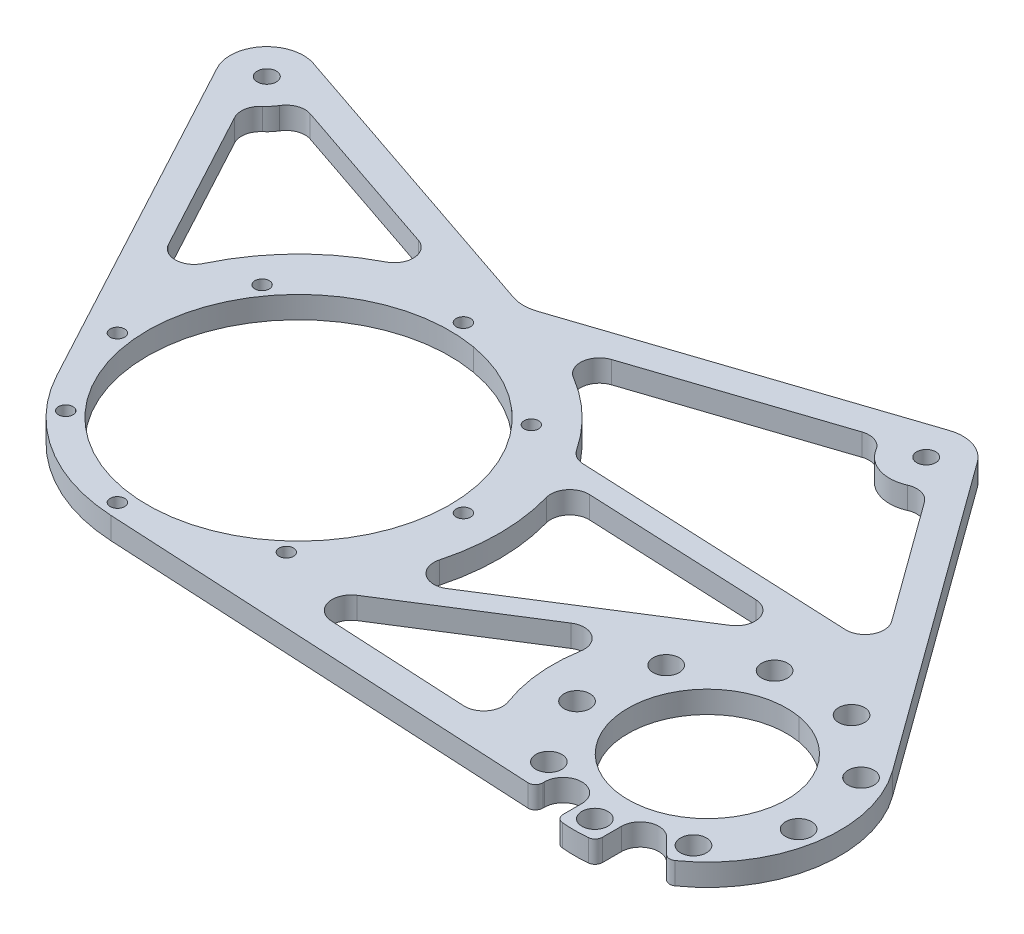
SolidWorks part; units mm, degrees
material "6061-T6 (SS)"
ref_plane "X-Y Datum" through (0, 0, 0) normal (0, 0, 1) x (1, 0, 0)
ref_plane "X-Z Datum" through (0, 0, 0) normal (0, 1, 0) x (1, 0, 0)
ref_plane "Y-Z Datum" through (0, 0, 0) normal (1, 0, 0) x (0, 0, -1)
sketch "Sketch2" plane through (0, -92.4008, 0) normal (0, 1, 0) x (1, 0, 0)
  line L0 (-504.3573, -163.648) -> (-504.3573, -170.2207) construction
  line L1 (-490.6797, -170.2207) -> (-490.6797, -163.648) construction
  line L2 (-479.5835, -159.0518) -> (-474.3186, -164.3167) construction
  line L3 (-504.3573, -163.648) -> (-504.3573, -170.2207)
  line L4 (-490.6797, -170.2207) -> (-490.6797, -163.648)
  line L5 (-479.5835, -159.0518) -> (-474.3186, -164.3167)
  line L6 (-777.24, 12.7) -> (-548.64, 12.7)
  line L7 (-538.3646, 7.4636) -> (-460.3214, -99.9818)
  line L9 (-788.4277, -6.0104) -> (-723.8302, -126.2521)
  line L10 (-517.3573, -164.225) -> (-517.3573, -163.648) construction
  line L11 (-517.3573, -164.225) -> (-517.3573, -163.648)
  line L12 (-672.5249, -158.7794) -> (-519.8973, -166.765)
  line L13 (-669.29, -96.9515) -> (-497.5185, -127) construction
  arc A0 (-521.206, -166.4019) -> (-517.3573, -164.225) centre (-519.8973, -164.225) ccw construction
  arc A1 (-504.3573, -163.648) -> (-517.3573, -163.648) centre (-510.8573, -163.648) ccw construction
  arc A2 (-504.3573, -170.2207) -> (-502.0687, -172.7483) centre (-501.8173, -170.2207) ccw construction
  arc A3 (-502.0687, -172.7483) -> (-492.9683, -172.7483) centre (-497.5185, -127) ccw construction
  arc A4 (-492.9683, -172.7483) -> (-490.6797, -170.2207) centre (-493.2197, -170.2207) ccw construction
  arc A5 (-479.5835, -159.0518) -> (-490.6797, -163.648) centre (-484.1797, -163.648) ccw construction
  arc A6 (-474.3186, -164.3167) -> (-471.0608, -164.5979) centre (-472.5226, -162.5207) ccw construction
  arc A7 (-471.0608, -164.5979) -> (-521.206, -166.4019) centre (-497.5185, -127) ccw construction
  circle A8 centre (-669.29, -96.9515) radius 52.3875 construction
  circle A9 centre (-669.29, -96.9515) radius 61.9125 construction
  circle A10 centre (-548.64, 0) radius 12.7 construction
  circle A11 centre (-777.24, 0) radius 12.7 construction
  arc A12 (-521.206, -166.4019) -> (-517.3573, -164.225) centre (-519.8973, -164.225) ccw
  arc A13 (-504.3573, -163.648) -> (-517.3573, -163.648) centre (-510.8573, -163.648) ccw
  arc A14 (-504.3573, -170.2207) -> (-502.0687, -172.7483) centre (-501.8173, -170.2207) ccw
  arc A15 (-502.0687, -172.7483) -> (-492.9683, -172.7483) centre (-497.5185, -127) ccw
  arc A16 (-492.9683, -172.7483) -> (-490.6797, -170.2207) centre (-493.2197, -170.2207) ccw
  arc A17 (-479.5835, -159.0518) -> (-490.6797, -163.648) centre (-484.1797, -163.648) ccw
  arc A18 (-474.3186, -164.3167) -> (-471.0608, -164.5979) centre (-472.5226, -162.5207) ccw
  arc A19 (-471.0608, -164.5979) -> (-521.206, -166.4019) centre (-497.5185, -127) ccw
  circle A20 centre (-669.29, -96.9515) radius 52.3875
  circle A21 centre (-669.29, -96.9515) radius 61.9125
  circle A22 centre (-548.64, 0) radius 12.7
  circle A23 centre (-777.24, 0) radius 12.7
  circle A24 centre (-711.7607, -135.1923) radius 2.5 construction
  circle A25 centre (-726.1269, -102.9253) radius 2.5 construction
  circle A26 centre (-715.5253, -63.3596) radius 2.5 construction
  circle A27 centre (-669.29, -39.8015) radius 2.5 construction
  circle A28 centre (-626.8193, -58.7107) radius 2.5 construction
  circle A29 centre (-612.14, -96.9515) radius 2.5 construction
  circle A30 centre (-631.0492, -139.4222) radius 2.5 construction
  circle A31 centre (-675.2638, -153.7884) radius 2.5 construction
  circle A32 centre (-711.7607, -135.1923) radius 2.5
  circle A33 centre (-726.1269, -102.9253) radius 2.5
  circle A34 centre (-715.5253, -63.3596) radius 2.5
  circle A35 centre (-669.29, -39.8015) radius 2.5
  circle A36 centre (-626.8193, -58.7107) radius 2.5
  circle A37 centre (-612.14, -96.9515) radius 2.5
  circle A38 centre (-631.0492, -139.4222) radius 2.5
  circle A39 centre (-675.2638, -153.7884) radius 2.5
  circle A40 centre (-497.5185, -127) radius 27.4955 construction
  circle A41 centre (-497.5185, -127) radius 27.4955
  circle A42 centre (-522.5872, -156.8757) radius 4.5 construction
  circle A43 centre (-535.926, -133.7723) radius 4.5 construction
  circle A44 centre (-531.2935, -107.5) radius 4.5 construction
  circle A45 centre (-510.8573, -90.352) radius 4.5 construction
  circle A46 centre (-484.1797, -90.352) radius 4.5 construction
  circle A47 centre (-463.7435, -107.5) radius 4.5 construction
  circle A48 centre (-459.111, -133.7723) radius 4.5 construction
  circle A49 centre (-472.4498, -156.8757) radius 4.5 construction
  circle A50 centre (-497.5185, -166) radius 4.5 construction
  circle A51 centre (-522.5872, -156.8757) radius 4.5
  circle A52 centre (-535.926, -133.7723) radius 4.5
  circle A53 centre (-531.2935, -107.5) radius 4.5
  circle A54 centre (-510.8573, -90.352) radius 4.5
  circle A55 centre (-484.1797, -90.352) radius 4.5
  circle A56 centre (-463.7435, -107.5) radius 4.5
  circle A57 centre (-459.111, -133.7723) radius 4.5
  circle A58 centre (-472.4498, -156.8757) radius 4.5
  circle A59 centre (-497.5185, -166) radius 4.5
  circle A60 centre (-777.24, 0) radius 3.3
  circle A61 centre (-548.64, 0) radius 3.3
  dimension "D1" = 6.6
  dimension "D2" = 6.6
extrude "Boss-Extrude1" add sketch "Sketch2" along normal blind 7.62 contours A21 A39 A38 A37 A36 A35 A34 A33 A32 A20 | A23 L9 A21 A19 L7 A22 L6 | A18 A19 A12 L11 A13 L3 A14 A15 A16 L4 A17 L5 A59 A58 A57 A56 A55 A54 A53 A52 A51 A41 | A23 A60 | A22 A61 | L13 A21 L12 A12 A19 region at (-510.8573, -92.4008, 155.8477) region at (-583.65, -92.4008, 141.3142) region at (-701.5034, -92.4008, 147.7617) region at (-625.8887, -92.4008, 39.3924) region at (-787.8317, -92.4008, -6.3332) region at (-536.903, -92.4008, -3.8128)
sketch "Sketch3" plane through (0, -92.4008, 0) normal (0, -1, 0) x (1, 0, 0)
  line L5 (-672.5249, 158.7794) -> (-519.8973, 166.765) construction
  line L6 (-788.4277, 6.0104) -> (-723.8302, 126.2521) construction
  line L7 (-538.3646, -7.4636) -> (-460.3214, 99.9818) construction
  line L16 (-777.24, -12.7) -> (-548.64, -12.7) construction
  line L19 (-474.3186, 164.3167) -> (-479.5835, 159.0518)
  line L20 (-490.6797, 163.648) -> (-490.6797, 170.2207)
  line L21 (-504.3573, 170.2207) -> (-504.3573, 163.648)
  line L22 (-517.3573, 163.648) -> (-517.3573, 164.225)
  line L23 (-474.3186, 164.3167) -> (-479.5835, 159.0518)
  line L24 (-490.6797, 163.648) -> (-490.6797, 170.2207)
  line L25 (-504.3573, 170.2207) -> (-504.3573, 163.648)
  line L26 (-517.3573, 163.648) -> (-517.3573, 164.225)
  line L28 (-672.5249, 158.7794) -> (-519.8973, 166.765)
  line L29 (-788.4277, 6.0104) -> (-723.8302, 126.2521)
  line L30 (-538.3646, -7.4636) -> (-460.3214, 99.9818)
  line L31 (-777.24, -12.7) -> (-548.64, -12.7)
  line L32 (-773.1635, -12.028) -> (-664.0361, 24.9569)
  line L33 (-664.0361, 24.9569) -> (-552.6443, -12.0522)
  circle A3 centre (-777.24, 0) radius 12.7
  circle A5 centre (-777.24, 0) radius 12.7
  circle A7 centre (-548.64, 0) radius 12.7
  circle A9 centre (-548.64, 0) radius 12.7
  circle A11 centre (-669.29, 96.9515) radius 61.9125
  circle A13 centre (-669.29, 96.9515) radius 61.9125
  circle A15 centre (-669.29, 96.9515) radius 52.3875
  circle A17 centre (-669.29, 96.9515) radius 52.3875
  circle A19 centre (-497.5185, 127) radius 27.4955
  circle A21 centre (-497.5185, 127) radius 27.4955
  circle A23 centre (-675.2638, 153.7884) radius 2.5
  circle A25 centre (-675.2638, 153.7884) radius 2.5
  circle A27 centre (-631.0492, 139.4222) radius 2.5
  circle A29 centre (-631.0492, 139.4222) radius 2.5
  circle A31 centre (-612.14, 96.9515) radius 2.5
  circle A33 centre (-612.14, 96.9515) radius 2.5
  circle A35 centre (-626.8193, 58.7107) radius 2.5
  circle A37 centre (-626.8193, 58.7107) radius 2.5
  circle A39 centre (-669.29, 39.8015) radius 2.5
  circle A41 centre (-669.29, 39.8015) radius 2.5
  circle A43 centre (-715.5253, 63.3596) radius 2.5
  circle A46 centre (-715.5253, 63.3596) radius 2.5
  circle A47 centre (-726.1269, 102.9253) radius 2.5
  circle A48 centre (-726.1269, 102.9253) radius 2.5
  circle A49 centre (-711.7607, 135.1923) radius 2.5
  circle A50 centre (-711.7607, 135.1923) radius 2.5
  circle A51 centre (-531.2935, 107.5) radius 4.5
  circle A52 centre (-531.2935, 107.5) radius 4.5
  circle A68 centre (-535.926, 133.7723) radius 4.5
  circle A69 centre (-535.926, 133.7723) radius 4.5
  circle A70 centre (-522.5872, 156.8757) radius 4.5
  circle A71 centre (-522.5872, 156.8757) radius 4.5
  circle A72 centre (-548.64, 0) radius 3.3
  circle A73 centre (-548.64, 0) radius 3.3
  circle A74 centre (-777.24, 0) radius 3.3
  circle A75 centre (-777.24, 0) radius 3.3
  circle A76 centre (-497.5185, 166) radius 4.5
  circle A77 centre (-497.5185, 166) radius 4.5
  circle A78 centre (-472.4498, 156.8757) radius 4.5
  circle A79 centre (-472.4498, 156.8757) radius 4.5
  circle A80 centre (-459.111, 133.7723) radius 4.5
  circle A81 centre (-459.111, 133.7723) radius 4.5
  circle A82 centre (-463.7435, 107.5) radius 4.5
  circle A83 centre (-463.7435, 107.5) radius 4.5
  circle A84 centre (-484.1797, 90.352) radius 4.5
  circle A85 centre (-484.1797, 90.352) radius 4.5
  circle A86 centre (-510.8573, 90.352) radius 4.5
  circle A87 centre (-510.8573, 90.352) radius 4.5
  arc A95 (-521.206, 166.4019) -> (-471.0608, 164.5979) centre (-497.5185, 127) ccw
  arc A96 (-471.0608, 164.5979) -> (-474.3186, 164.3167) centre (-472.5226, 162.5207) ccw
  arc A97 (-490.6797, 163.648) -> (-479.5835, 159.0518) centre (-484.1797, 163.648) ccw
  arc A98 (-490.6797, 170.2207) -> (-492.9683, 172.7483) centre (-493.2197, 170.2207) ccw
  arc A99 (-492.9683, 172.7483) -> (-502.0687, 172.7483) centre (-497.5185, 127) ccw
  arc A100 (-502.0687, 172.7483) -> (-504.3573, 170.2207) centre (-501.8173, 170.2207) ccw
  arc A101 (-517.3573, 163.648) -> (-504.3573, 163.648) centre (-510.8573, 163.648) ccw
  arc A102 (-517.3573, 164.225) -> (-521.206, 166.4019) centre (-519.8973, 164.225) ccw
  arc A103 (-521.206, 166.4019) -> (-471.0608, 164.5979) centre (-497.5185, 127) ccw
  arc A104 (-471.0608, 164.5979) -> (-474.3186, 164.3167) centre (-472.5226, 162.5207) ccw
  arc A105 (-490.6797, 163.648) -> (-479.5835, 159.0518) centre (-484.1797, 163.648) ccw
  arc A106 (-490.6797, 170.2207) -> (-492.9683, 172.7483) centre (-493.2197, 170.2207) ccw
  arc A107 (-492.9683, 172.7483) -> (-502.0687, 172.7483) centre (-497.5185, 127) ccw
  arc A108 (-502.0687, 172.7483) -> (-504.3573, 170.2207) centre (-501.8173, 170.2207) ccw
  arc A109 (-517.3573, 163.648) -> (-504.3573, 163.648) centre (-510.8573, 163.648) ccw
  arc A110 (-517.3573, 164.225) -> (-521.206, 166.4019) centre (-519.8973, 164.225) ccw
  point P96 (-664.0361, 24.9569)
  line M47 (-777.24, -12.7) -> (-548.64, -12.7)
  dimension "D24" = 0
  dimension "D25" = 0
  dimension "D26" = 109.1275
  dimension "D27" = 36.9849
  dimension "D1" = 0
  dimension "D2" = 0
  dimension "D3" = 0
  dimension "D4" = 0
  dimension "D5" = 0
  dimension "D6" = 0
  dimension "D7" = 0
  dimension "D8" = 0
  dimension "D9" = 0
  dimension "D10" = 0
  dimension "D11" = 0
  dimension "D12" = 0
  dimension "D13" = 0
  dimension "D14" = 0
  dimension "D15" = 0
  dimension "D16" = 0
  dimension "D17" = 0
  dimension "D18" = 0
  dimension "D19" = 0
  dimension "D20" = 0
  dimension "D21" = 0
  dimension "D22" = 0
  dimension "D23" = 0
ref_point "Point1"
ref_point "Point2"
ref_plane "Plane1" through (-669.29, -92.4008, 96.9515) normal (0.985, 0, 0.1723) x (0.1723, 0, -0.985)
ref_plane "Plane2" through (-497.5185, -92.4008, 127) normal (-0.985, 0, -0.1723) x (-0.1723, 0, 0.985)
split line "Split Line1"
split line "Split Line2"
ref_axis "Axis1" through (-669.29, -84.7808, 96.9515) along (0, -1, 0)
ref_axis "Axis2" through (-497.5185, -84.7808, 127) along (0, -1, 0)
extrude "Cut-Extrude1" cut sketch "Sketch3" against normal through all contours A9 L33 L32 A5 M47 region at (-663.2926, -92.4008, -0.149)
fillet "Fillet2" radius 12.7 1 edges at (-664.0361, -88.5908, 24.9569)
sketch "Sketch4" plane through (0, -92.4008, 0) normal (0, -1, 0) x (1, 0, 0)
  line L0 (-672.5249, 158.7794) -> (-519.8973, 166.765) construction
  line L1 (-538.3646, -7.4636) -> (-460.3214, 99.9818) construction
  line L2 (-788.4277, 6.0104) -> (-723.8302, 126.2521) construction
  line L3 (-773.1635, -12.028) -> (-664.0361, 24.9569) construction
  line L4 (-517.3573, 163.648) -> (-517.3573, 164.225)
  line L5 (-474.3186, 164.3167) -> (-479.5835, 159.0518)
  line L6 (-490.6797, 163.648) -> (-490.6797, 170.2207)
  line L7 (-504.3573, 170.2207) -> (-504.3573, 163.648)
  line L8 (-517.3573, 163.648) -> (-517.3573, 164.225)
  line L9 (-474.3186, 164.3167) -> (-479.5835, 159.0518)
  line L10 (-490.6797, 163.648) -> (-490.6797, 170.2207)
  line L11 (-504.3573, 170.2207) -> (-504.3573, 163.648)
  line L12 (-664.0361, 24.9569) -> (-552.6443, -12.0522) construction
  line L13 (-777.24, -12.7) -> (-548.64, -12.7) construction
  line L14 (-672.5249, 158.7794) -> (-519.8973, 166.765)
  line L15 (-538.3646, -7.4636) -> (-460.3214, 99.9818)
  line L16 (-788.4277, 6.0104) -> (-723.8302, 126.2521)
  line L17 (-773.1635, -12.028) -> (-664.0361, 24.9569)
  line L18 (-664.0361, 24.9569) -> (-552.6443, -12.0522)
  line L19 (-777.24, -12.7) -> (-548.64, -12.7)
  line L20 (-736.857, 80.5359) -> (-782.5267, -4.4737)
  line L21 (-782.5267, -4.4737) -> (-683.866, 28.9639)
  line L22 (-542.9794, 155.3834) -> (-623.3807, 151.1768)
  line L23 (-623.3807, 151.1768) -> (-544.5668, 101.3333)
  line L24 (-610.432, 133.9718) -> (-514.4002, 73.2395)
  line L25 (-514.4002, 73.2395) -> (-605.5685, 69.1245)
  line L26 (-648.653, 30.5521) -> (-561.2496, 1.5129)
  line L27 (-609.5837, 61.3155) -> (-497.2823, 66.3843)
  line L28 (-497.2823, 66.3843) -> (-539.2721, 8.5751)
  circle A1 centre (-669.29, 96.9515) radius 52.3875
  circle A2 centre (-669.29, 96.9515) radius 52.3875
  circle A3 centre (-669.29, 96.9515) radius 61.9125
  circle A4 centre (-669.29, 96.9515) radius 61.9125
  circle A5 centre (-548.64, 0) radius 12.7
  circle A6 centre (-548.64, 0) radius 12.7
  circle A7 centre (-777.24, 0) radius 12.7
  circle A8 centre (-777.24, 0) radius 12.7
  circle A9 centre (-669.29, 39.8015) radius 2.5
  circle A10 centre (-669.29, 39.8015) radius 2.5
  circle A11 centre (-626.8193, 58.7107) radius 2.5
  circle A12 centre (-626.8193, 58.7107) radius 2.5
  circle A13 centre (-612.14, 96.9515) radius 2.5
  circle A14 centre (-612.14, 96.9515) radius 2.5
  circle A15 centre (-631.0492, 139.4222) radius 2.5
  circle A16 centre (-631.0492, 139.4222) radius 2.5
  circle A17 centre (-675.2638, 153.7884) radius 2.5
  circle A18 centre (-675.2638, 153.7884) radius 2.5
  circle A19 centre (-497.5185, 127) radius 27.4955
  circle A20 centre (-497.5185, 127) radius 27.4955
  circle A21 centre (-535.926, 133.7723) radius 4.5
  circle A22 centre (-535.926, 133.7723) radius 4.5
  circle A23 centre (-531.2935, 107.5) radius 4.5
  circle A24 centre (-531.2935, 107.5) radius 4.5
  circle A25 centre (-711.7607, 135.1923) radius 2.5
  circle A26 centre (-711.7607, 135.1923) radius 2.5
  circle A27 centre (-726.1269, 102.9253) radius 2.5
  circle A28 centre (-726.1269, 102.9253) radius 2.5
  circle A29 centre (-715.5253, 63.3596) radius 2.5
  circle A30 centre (-715.5253, 63.3596) radius 2.5
  circle A31 centre (-472.4498, 156.8757) radius 4.5
  circle A32 centre (-472.4498, 156.8757) radius 4.5
  circle A33 centre (-497.5185, 166) radius 4.5
  circle A34 centre (-497.5185, 166) radius 4.5
  circle A35 centre (-777.24, 0) radius 3.3
  circle A36 centre (-777.24, 0) radius 3.3
  circle A37 centre (-548.64, 0) radius 3.3
  circle A38 centre (-548.64, 0) radius 3.3
  circle A39 centre (-522.5872, 156.8757) radius 4.5
  circle A40 centre (-522.5872, 156.8757) radius 4.5
  circle A41 centre (-510.8573, 90.352) radius 4.5
  circle A42 centre (-510.8573, 90.352) radius 4.5
  circle A43 centre (-484.1797, 90.352) radius 4.5
  circle A44 centre (-484.1797, 90.352) radius 4.5
  circle A45 centre (-463.7435, 107.5) radius 4.5
  circle A46 centre (-463.7435, 107.5) radius 4.5
  circle A47 centre (-459.111, 133.7723) radius 4.5
  circle A48 centre (-459.111, 133.7723) radius 4.5
  arc A49 (-683.866, 28.9639) -> (-736.857, 80.5359) centre (-669.29, 96.9515) cw
  arc A50 (-542.9794, 155.3834) -> (-544.5668, 101.3333) centre (-497.5185, 127) ccw
  arc A51 (-610.432, 133.9718) -> (-605.5685, 69.1245) centre (-669.29, 96.9515) cw
  arc A52 (-648.653, 30.5521) -> (-609.5837, 61.3155) centre (-669.29, 96.9515) ccw
  arc A56 (-517.3573, 164.225) -> (-521.206, 166.4019) centre (-519.8973, 164.225) ccw
  arc A57 (-521.206, 166.4019) -> (-471.0608, 164.5979) centre (-497.5185, 127) ccw
  arc A58 (-471.0608, 164.5979) -> (-474.3186, 164.3167) centre (-472.5226, 162.5207) ccw
  arc A59 (-490.6797, 163.648) -> (-479.5835, 159.0518) centre (-484.1797, 163.648) ccw
  arc A60 (-490.6797, 170.2207) -> (-492.9683, 172.7483) centre (-493.2197, 170.2207) ccw
  arc A61 (-492.9683, 172.7483) -> (-502.0687, 172.7483) centre (-497.5185, 127) ccw
  arc A62 (-502.0687, 172.7483) -> (-504.3573, 170.2207) centre (-501.8173, 170.2207) ccw
  arc A63 (-517.3573, 163.648) -> (-504.3573, 163.648) centre (-510.8573, 163.648) ccw
  arc A64 (-517.3573, 164.225) -> (-521.206, 166.4019) centre (-519.8973, 164.225) ccw
  arc A65 (-521.206, 166.4019) -> (-471.0608, 164.5979) centre (-497.5185, 127) ccw
  arc A66 (-471.0608, 164.5979) -> (-474.3186, 164.3167) centre (-472.5226, 162.5207) ccw
  arc A67 (-490.6797, 163.648) -> (-479.5835, 159.0518) centre (-484.1797, 163.648) ccw
  arc A68 (-490.6797, 170.2207) -> (-492.9683, 172.7483) centre (-493.2197, 170.2207) ccw
  arc A69 (-492.9683, 172.7483) -> (-502.0687, 172.7483) centre (-497.5185, 127) ccw
  arc A70 (-502.0687, 172.7483) -> (-504.3573, 170.2207) centre (-501.8173, 170.2207) ccw
  arc A71 (-517.3573, 163.648) -> (-504.3573, 163.648) centre (-510.8573, 163.648) ccw
  point P115 (-561.2494, 1.5144)
  point P117 (-647.1131, 28.9639)
  point P118 (-645.4628, 29.9334)
  dimension "D26" = 7.62
  dimension "D29" = 7.62
  dimension "D30" = 7.62
  dimension "D35" = 10.16
  dimension "D39" = 7.62
  dimension "D27" = 10.16
  dimension "D28" = 10.16
  dimension "D31" = 10.16
  dimension "D32" = 7.62
  dimension "D33" = 93.2524
  dimension "D34" = 49.8435
  dimension "D36" = 91.1683
  dimension "D37" = 4.1149
  dimension "D38" = 10.16
  dimension "D40" = 7.62
  dimension "D1" = 0
  dimension "D2" = 0
  dimension "D3" = 0
  dimension "D4" = 0
  dimension "D5" = 0
  dimension "D6" = 0
  dimension "D7" = 0
  dimension "D8" = 0
  dimension "D9" = 0
  dimension "D10" = 0
  dimension "D11" = 0
  dimension "D12" = 0
  dimension "D13" = 0
  dimension "D14" = 0
  dimension "D15" = 0
  dimension "D16" = 0
  dimension "D17" = 0
  dimension "D18" = 0
  dimension "D19" = 0
  dimension "D20" = 0
  dimension "D21" = 0
  dimension "D22" = 0
  dimension "D23" = 0
  dimension "D24" = 0
  dimension "D25" = 0
extrude "Cut-Extrude2" cut sketch "Sketch4" against normal through all contours L21 A49 L20 A8 | A52 L26 A6 L28 L27 | L24 A51 L25 | A50 L22 L23 region at (-736.5247, -92.4008, 33.3857) region at (-569.3531, -92.4008, 38.1987) region at (-573.6295, -92.4008, 137.0229) region at (-573.0084, -92.4008, 90.7995)
fillet "Fillet3" radius 6.604 15 edges at (-544.5668, -88.5908, 101.3333) (-542.9794, -88.5908, 155.3834) (-623.3807, -88.5908, 151.1768) (-514.4002, -88.5908, 73.2395) (-605.5685, -88.5908, 69.1245) (-610.432, -88.5908, 133.9718) (-497.2823, -88.5908, 66.3843) (-609.5837, -88.5908, 61.3155) (-648.653, -88.5908, 30.5521) (-561.2496, -88.5908, 1.5129) (-539.2721, -88.5908, 8.5751) (-764.6397, -88.5908, 1.5885) (-773.5886, -88.5908, 12.1638) (-683.866, -88.5908, 28.9639) (-736.857, -88.5908, 80.5359)
split line "Split Line3"
sketch "Sketch2<4>" plane through (0, -92.4008, 0) normal (0, 1, 0) x (1, 0, 0) same geometry as "Sketch2"
